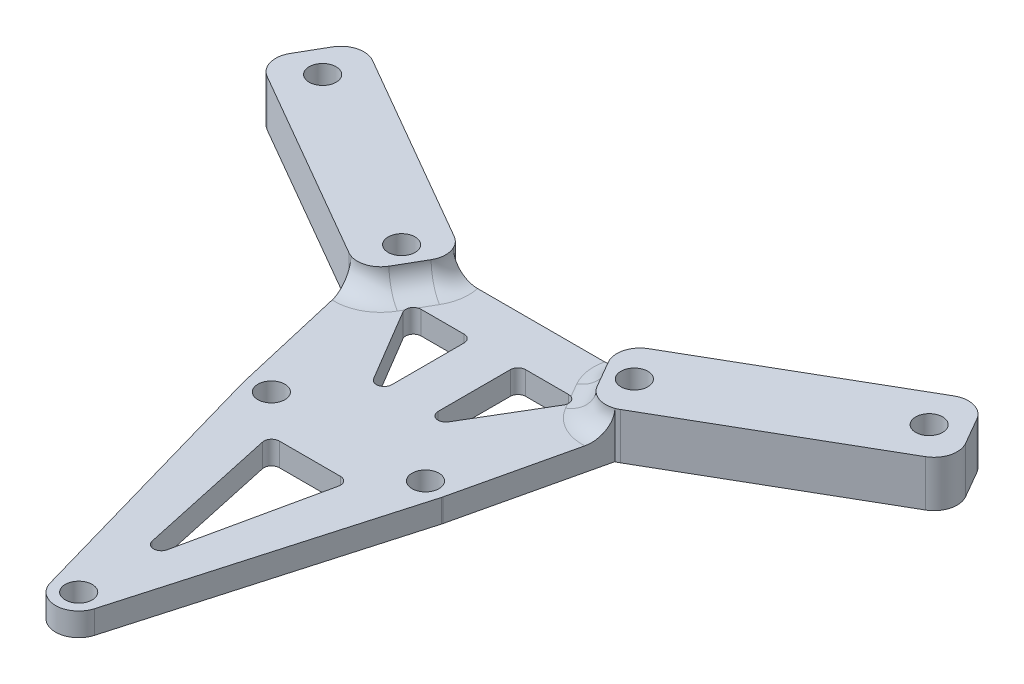
SolidWorks part; units mm, degrees
ref_plane "前视基准面" through (0, 0, 0) normal (0, 0, 1) x (1, 0, 0)
ref_plane "上视基准面" through (0, 0, 0) normal (0, 1, 0) x (1, 0, 0)
ref_plane "右视基准面" through (0, 0, 0) normal (1, 0, 0) x (0, 0, -1)
other "Configuration Table"
sketch "草图1" plane through (0, 0, 0) normal (0, 1, 0) x (1, 0, 0)
  line L0 (-15.1, 0) -> (15.1, 0)
  line L3 (0, 0) -> (0, -65) construction
  line L4 (-15.1, -3) -> (15.1, -3) construction
  line L5 (-12.9054, -25.7513) -> (-2.8846, -60.8242)
  line L6 (-18.0225, -3.6775) -> (-12.9054, -25.7513)
  line L7 (-10, -25) -> (10, -25) construction
  line L8 (18.0225, -3.6775) -> (12.9054, -25.7513)
  line L9 (12.9054, -25.7513) -> (2.8846, -60.8242)
  line L28 (3, -6) -> (11.325, -6)
  line L29 (-10, -22) -> (10, -22) construction
  line L30 (-3, -60) -> (-3, -3) construction
  line L31 (3, -60) -> (3, -3) construction
  line L32 (-11.325, -6) -> (-3, -6)
  line L33 (-6.9204, -25) -> (-12.1775, -2.3225) construction
  line L34 (7.0775, -24.3225) -> (12.1775, -2.3225) construction
  line L35 (-11.325, -6) -> (-3, -20)
  line L36 (-3, -20) -> (-3, -6)
  line L37 (11.325, -6) -> (3, -20)
  line L38 (3, -20) -> (3, -6)
  line L39 (-10, -28) -> (10, -28) construction
  line L40 (0, -57) -> (-7.1404, -24.0928) construction
  line L41 (0, -57) -> (7.0775, -24.3225) construction
  line L42 (-5.2077, -30) -> (5.2077, -30)
  line L43 (5.2077, -30) -> (0, -54)
  line L44 (0, -54) -> (-5.2077, -30)
  circle A0 centre (-15.1, -3) radius 1.75
  circle A1 centre (15.1, -3) radius 1.75
  circle A2 centre (0, -60) radius 1.75
  circle A3 centre (-15.1, -3) radius 3
  circle A4 centre (15.1, -3) radius 3
  circle A5 centre (0, -60) radius 3
  circle A6 centre (-10, -25) radius 1.75
  circle A7 centre (10, -25) radius 1.75
  circle A8 centre (-10, -25) radius 3
  circle A9 centre (10, -25) radius 3
  point P5 (0, 0)
  point P12 (0, -3)
  point P15 (0, -25)
  point P58 (0, -30)
  dimension "D3" = 3.5
  dimension "D6" = 6
  dimension "D1" = 6
  dimension "D7" = 20
  dimension "D9" = 6
  dimension "D10" = 6
  dimension "D14" = 3.5
  dimension "D15" = 3.5
  dimension "D16" = 3.5
  dimension "D17" = 3.5
  dimension "D2" = 65
  dimension "D4" = 30.2
  dimension "D5" = 57
  dimension "D8" = 35
  dimension "D11" = 2
  dimension "D12" = 2
  dimension "D13" = 6
extrude "凸台-拉伸1" add sketch "草图1" along normal blind 3 contours A8 A6 | A9 L8 A4 L0 A3 L6 A8 L5 A5 L9 | A9 A7 | A4 A1 | A3 A0 | A5 A2 region at (0, 0, 23.2736) region at (-13.0387, 0, 0.9387) region at (17.1613, 0, 0.9387) region at (-10.3313, 0, 22.1037) region at (12.8223, 0, 25.7298) region at (-0.4043, 0, 57.113)
sketch "草图2" plane through (0, 0, 0) normal (0, 1, 0) x (1, 0, 0)
  line L0 (-15.1, 0) -> (15.1, 0) construction
  line L1 (15.0019, -8.8301) -> (45.3128, 8.6699)
  line L2 (15.0019, -8.8301) -> (10.0019, -0.1699)
  line L3 (10.0019, -0.1699) -> (40.3128, 17.3301)
  line L4 (45.3128, 8.6699) -> (40.3128, 17.3301)
  line L5 (-42.8128, 13) -> (-12.5019, -4.5) construction
  line L6 (-45.3128, 8.6699) -> (-15.0019, -8.8301)
  line L7 (-45.3128, 8.6699) -> (-40.3128, 17.3301)
  line L8 (-40.3128, 17.3301) -> (-10.0019, -0.1699)
  line L9 (-15.0019, -8.8301) -> (-10.0019, -0.1699)
  line L10 (12.5019, -4.5) -> (42.8128, 13) construction
  circle A0 centre (39.3487, 11) radius 1.75
  circle A1 centre (-15.1, -3) radius 1.75
  circle A2 centre (-39.3487, 11) radius 1.75
  circle A3 centre (15.1, -3) radius 1.75
  point P4 (-15.1, -3)
  point P5 (0, 0)
  point P6 (15.1, -3)
  point P24 (0, 0)
  point P26 (0, 0)
  point P29 (0, 0)
  point P30 (0, 0)
  dimension "D3" = 3
  dimension "D4" = 35
  dimension "D7" = 3.5
  dimension "D11" = 3.5
  dimension "D13" = 3.5
  dimension "D14" = 3.5
  dimension "D1" = 35
  dimension "D2" = 10
  dimension "D5" = 10
  dimension "D6" = 3
  dimension "D8" = 30
  dimension "D9" = 30
  dimension "D10" = 4
  dimension "D12" = 4
extrude "凸台-拉伸3" add sketch "草图2" along normal blind 6
fillet "圆角1" radius 3 8 edges at (15.0019, 4.5, 8.8301) (10.0019, 4.5, 0.1699) (-40.3128, 3, -17.3301) (40.3128, 3, -17.3301) (45.3128, 3, -8.6699) (-10.0019, 4.5, 0.1699) (-15.0019, 4.5, 8.8301) (-45.3128, 3, -8.6699)
fillet "圆角2" radius 3 6 edges at (15.0731, 3, 7.5508) (11.1029, 3, 1.3988) (-11.1029, 3, 1.3988) (-15.0731, 3, 7.5508) (12.5019, 3, 4.5) (-12.5019, 3, 4.5)
fillet "圆角4" radius 1 9 edges at (0, 1.5, 54) (3, 1.5, 20) (-3, 1.5, 20) (11.325, 1.632, 6) (-3, 1.5, 6) (5.2077, 1.5, 30) (3, 1.5, 6) (-11.325, 1.632, 6) (-5.2077, 1.5, 30)
